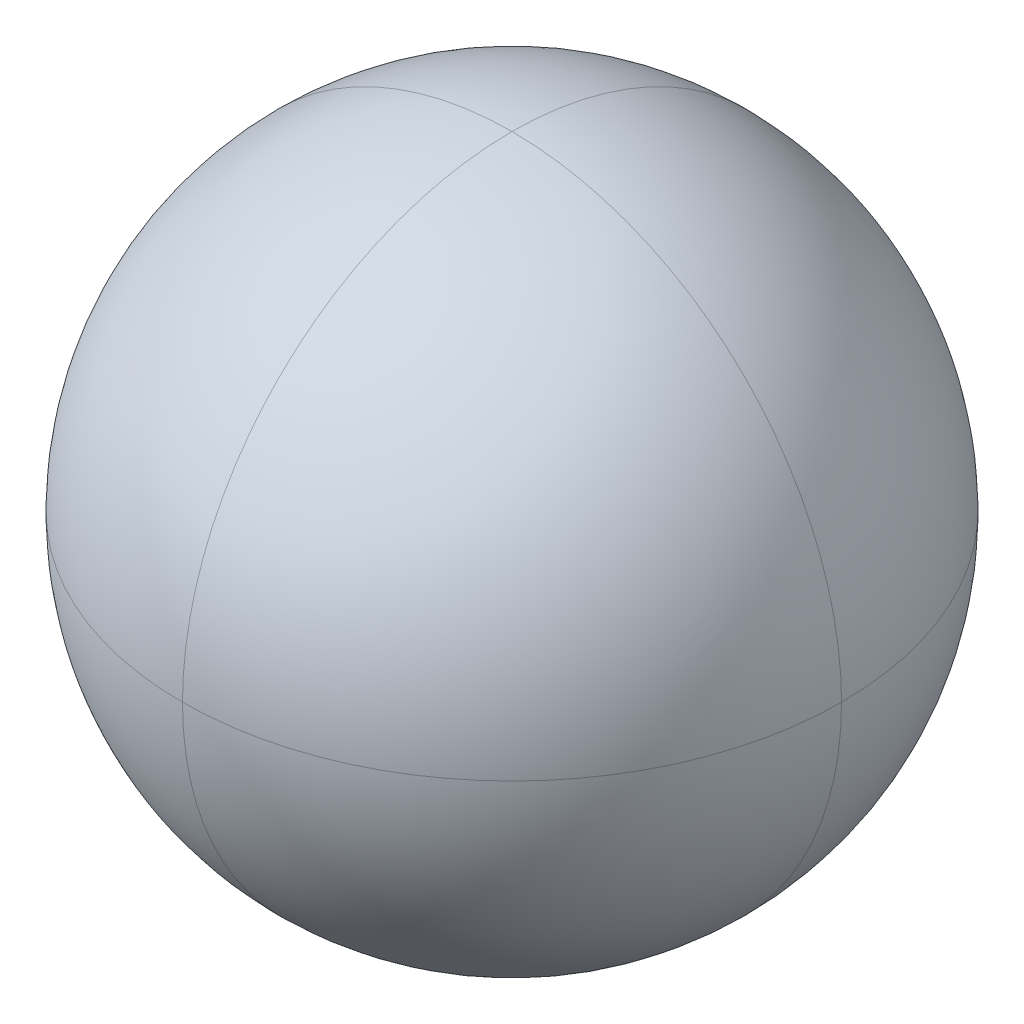
SolidWorks part; units mm, degrees
ref_plane "Front Plane" through (0, 0, 0) normal (0, 0, 1) x (1, 0, 0)
ref_plane "Top Plane" through (0, 0, 0) normal (0, 1, 0) x (1, 0, 0)
ref_plane "Right Plane" through (0, 0, 0) normal (1, 0, 0) x (0, 0, -1)
sketch "Sketch1" plane through (0, 0, 0) normal (0, 0, 1) x (1, 0, 0)
  line L1 (-50, -50) -> (50, -50)
  line L2 (-50, -50) -> (-50, 50)
  line L3 (-50, 50) -> (50, 50)
  line L4 (50, -50) -> (50, 50)
  line L5 (-50, -50) -> (50, 50) construction
  line L6 (-50, 50) -> (50, -50) construction
  point P0 (0, 0)
  dimension "D1" = 100
  dimension "D2" = 100
extrude "Boss-Extrude1" add sketch "Sketch1" along normal mid plane 100
fillet "Fillet1" radius 50 12 edges at (-50, 0, 50) (0, -50, 50) (50, 0, 50) (0, -50, -50) (-50, 0, -50) (0, 50, -50) (50, 0, -50) (50, -50, 0) (-50, -50, 0) (-50, 50, 0) (50, 50, 0) (0, 50, 50)
